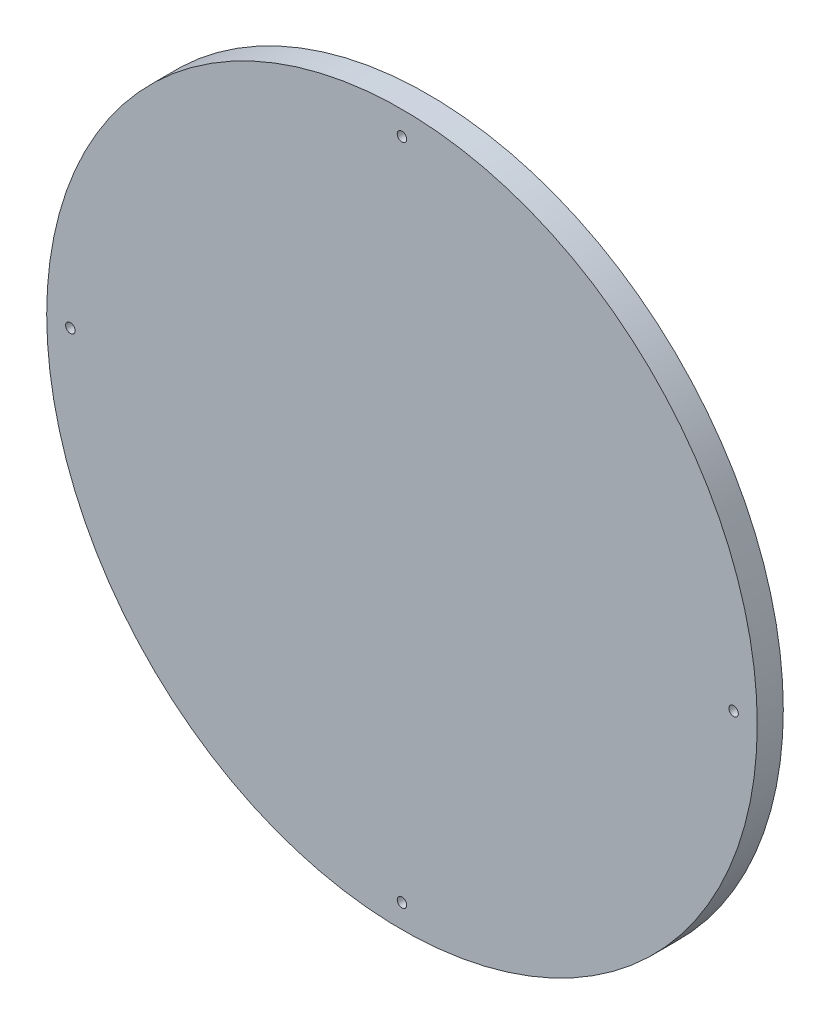
SolidWorks part; units mm, degrees
ref_plane "Plan de face" through (0, 0, 0) normal (0, 0, 1) x (1, 0, 0)
ref_plane "Plan de dessus" through (0, 0, 0) normal (0, 1, 0) x (1, 0, 0)
ref_plane "Plan de droite" through (0, 0, 0) normal (1, 0, 0) x (0, 0, -1)
sketch "Esquisse1" plane through (0, 0, 0) normal (0, 0, 1) x (1, 0, 0)
  circle A0 centre (0, 0) radius 300
extrude "Boss.-Extru.1" add sketch "Esquisse1" along normal blind 22
sketch "Esquisse2" plane through (0, 0, 22) normal (0, 0, 1) x (1, 0, 0)
  circle A0 centre (0, 280) radius 4
  dimension "D1" = 280
extrude "Enlèv. mat.-Extru.1" cut sketch "Esquisse2" against normal through all
sketch "Esquisse3" plane through (0, 0, 0) normal (1, 0, 0) x (0, 0, -1)
  line L0 (133.9123, 0) -> (-227.7324, 0) construction
pattern_circular "Répétition circulaire1" count 4 every 90 about axis through (0, 0, 22) along (0, 0, 1) of "Enlèv. mat.-Extru.1"
